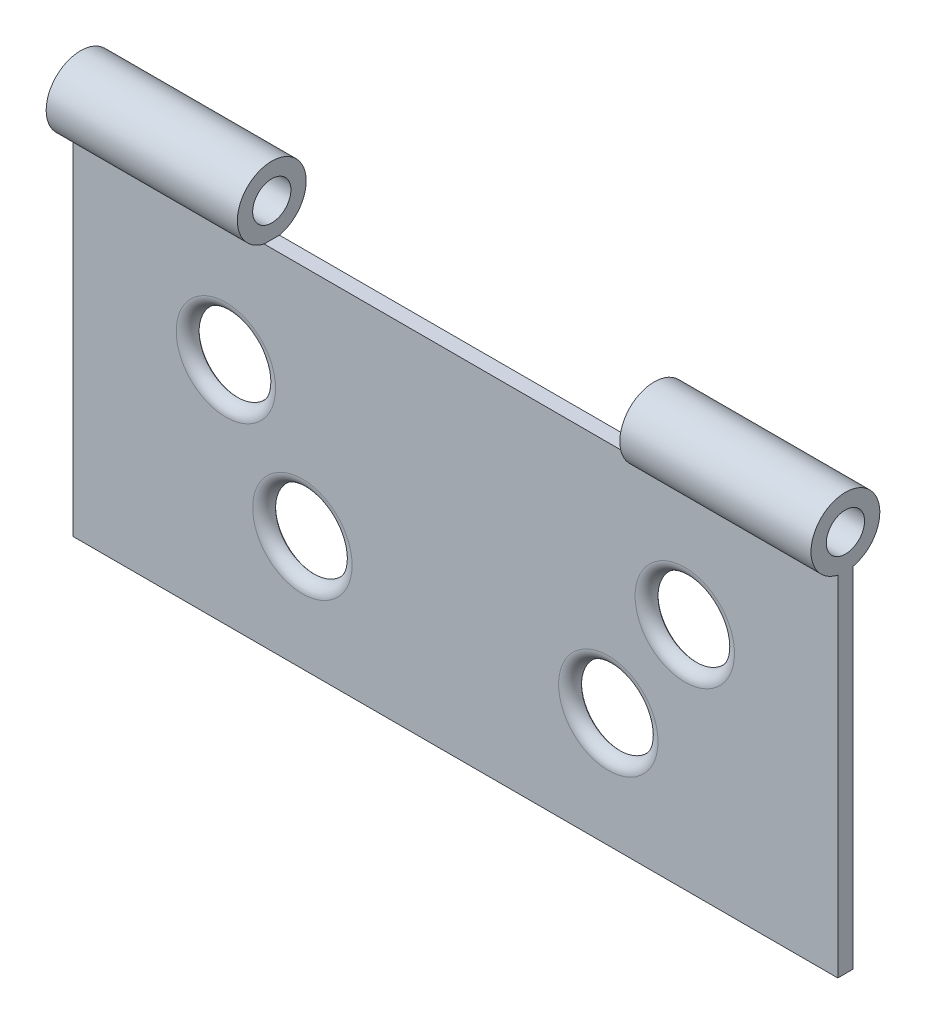
SolidWorks part; units mm, degrees
material "Liga de aço fundido"
ref_plane "Plano frontal" through (0, 0, 0) normal (0, 0, 1) x (1, 0, 0)
ref_plane "Plano superior" through (0, 0, 0) normal (0, 1, 0) x (1, 0, 0)
ref_plane "Plano direito" through (0, 0, 0) normal (1, 0, 0) x (0, 0, -1)
sketch "Esboço1" plane through (0, 0, 0) normal (0, 0, 1) x (1, 0, 0)
  line L2 (0, 0) -> (0, -50)
  line L3 (0, -50) -> (-100, -50)
  line L4 (-100, 0) -> (-100, -50)
  line L5 (-100, 0) -> (0, 0)
  circle A4 centre (-30, -35) radius 5
  circle A5 centre (-80, -20) radius 5
  circle A6 centre (-70, -35) radius 5
  circle A7 centre (-20, -20) radius 5
  dimension "D3" = 20
  dimension "D10" = 10
  dimension "D11" = 15
  dimension "D1" = 50
  dimension "D2" = 100
  dimension "D4" = 30
  dimension "D5" = 20
  dimension "D6" = 30
  dimension "D7" = 30
extrude "Ressalto-extrusão1" add sketch "Esboço1" along normal blind 2 contours L4 L3 L2 region at (-50, -24.8324, 0)
fillet "Filete1" radius 1.5 4 edges at (-15, -20, 2) (-25, -35, 2) (-65, -35, 2) (-75, -20, 2)
fillet "Filete2" radius 1.5 4 edges at (-65, -35, 0) (-75, -20, 0) (-25, -35, 0) (-15, -20, 0)
sketch "Esboço2" plane through (0, 0, 0) normal (1, 0, 0) x (0, 0, -1)
  line L0 (-2, 0) -> (0, 0) construction
  circle A0 centre (-1, 0) radius 2.5
  circle A1 centre (-1, 0) radius 4.5
  dimension "D1" = 2
  dimension "D2" = 9
extrude "Ressalto-extrusão2" add sketch "Esboço2" against normal through all
sketch "Esboço3" plane through (0, 0, 0) normal (1, 0, 0) x (0, 0, -1)
  arc A0 (0, -2.2913) -> (-2, -2.2913) centre (-1, 0) ccw construction
  arc A1 (0, -2.2913) -> (-2, -2.2913) centre (-1, 0) ccw
  circle A2 centre (-1, 0) radius 2.5
  line M5 (-2, 0) -> (-2, -2.2913)
  arc M6 (-2, -2.2913) -> (0, -2.2913) centre (-1, 0) cw
  line M7 (0, -2.2913) -> (0, 0)
  line M8 (0, 0) -> (-2, 0)
extrude "Corte-extrusão1" cut sketch "Esboço3" against normal through all contours M5 M8 M7 M6 | A2 M5 M7 M8 region at (0, 0.4005, 1) region at (0, -1.2166, 1)
sketch "Esboço4" plane through (0, 0, 0) normal (0, 0, -1) x (-1, 0, 0)
  line L4 (100, -50) -> (100, -4.3875)
  line L5 (100, -4.3875) -> (0, -4.3875)
  line L6 (0, -4.3875) -> (0, -50)
  line L7 (0, -50) -> (100, -50)
  line L8 (100, -50) -> (100, -4.3875)
  line L10 (0, -4.3875) -> (0, -50)
  line L11 (0, -50) -> (100, -50)
  line L13 (75, -4.3875) -> (100, -4.3875) construction
  line L14 (75, -4.3875) -> (75, -2.2913) construction
  line L15 (25, -4.3875) -> (0, -4.3875) construction
  line L17 (75, -4.3875) -> (25, -4.3875)
  line L18 (75, -4.3875) -> (75, 15.6125)
  line L25 (100, -50) -> (100, -4.3875)
  line L26 (100, -4.3875) -> (0, -4.3875)
  line L27 (0, -4.3875) -> (0, -50)
  line L28 (0, -50) -> (100, -50)
  line L31 (100, -50) -> (100, -4.3875)
  line L32 (100, -4.3875) -> (0, -4.3875)
  line L33 (0, -4.3875) -> (0, -50)
  line L34 (0, -50) -> (100, -50)
  line L36 (75, 15.6125) -> (25, 15.6125)
  line L37 (25, -4.3875) -> (25, 15.6125)
  line M10 (100, -4.3875) -> (0, -4.3875)
  dimension "D2" = 0
  dimension "D3" = 25
  dimension "D4" = 25
  dimension "D1" = 0
extrude "Corte-extrusão2" cut sketch "Esboço4" against normal through all and the other way blind 10 contours M10 | L18 L17 L37 L36 region at (-50, 5.6125, 0)
